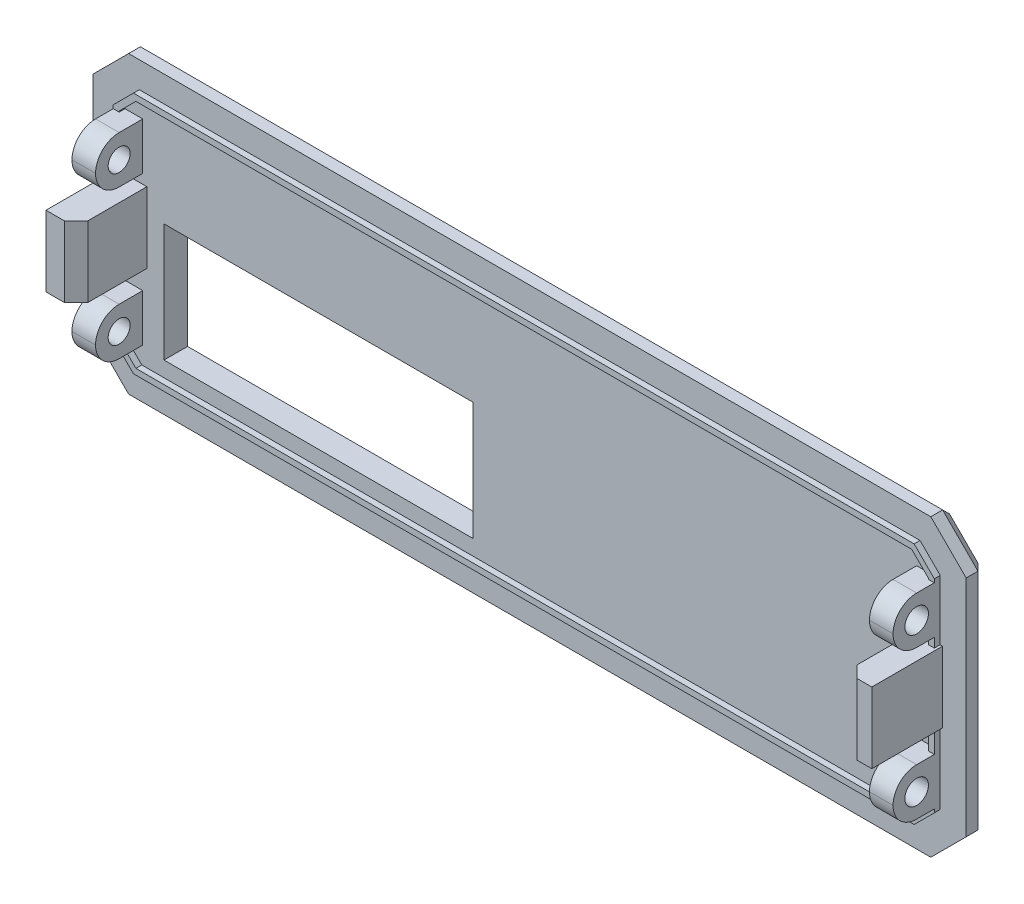
SolidWorks part; units mm, degrees
ref_plane "前视基准面" through (0, 0, 0) normal (0, 0, 1) x (1, 0, 0)
ref_plane "上视基准面" through (0, 0, 0) normal (0, 1, 0) x (1, 0, 0)
ref_plane "右视基准面" through (0, 0, 0) normal (1, 0, 0) x (0, 0, -1)
other "Configuration Table"
sketch "草图1" plane through (0, 0, 0) normal (0, 0, 1) x (1, 0, 0)
  line L0 (-39.7638, 4.7992) -> (-36.7638, 7.7992)
  line L5 (-36.7638, 7.7992) -> (31.2362, 7.7992)
  line L6 (-39.7638, 4.7992) -> (-39.7638, -14.2008)
  line L7 (-36.7638, -17.2008) -> (31.2362, -17.2008)
  line L8 (34.2362, 4.7992) -> (34.2362, -14.2008)
  line L9 (-39.7638, -14.2008) -> (-36.7638, -17.2008)
  line L10 (31.2362, -17.2008) -> (34.2362, -14.2008)
  line L11 (31.2362, 7.7992) -> (34.2362, 4.7992)
  point P0 (-39.7638, 7.7992)
  point P1 (34.2362, -17.2008)
  point P2 (-39.7638, -17.2008)
  point P3 (34.2362, 7.7992)
  dimension "D1" = 74
  dimension "D2" = 25
extrude "凸台-拉伸1" add sketch "草图1" along normal blind 2
chamfer "倒角1" distance 1 angle 45 8 edges at (-38.2638, 6.2992, 0) (-2.7638, -17.2008, 0) (-39.7638, -4.7008, 0) (-38.2638, -15.7008, 0) (32.7362, -15.7008, 0) (34.2362, -4.7008, 0) (32.7362, 6.2992, 0) (-2.7638, 7.7992, 0)
sketch "草图3" plane through (0, 0, 2) normal (0, 0, 1) x (1, 0, 0)
  line L0 (-36.7638, 7.7992) -> (31.2362, 7.7992) construction
  line L1 (-37.5638, 3.5992) -> (-35.5638, 3.5992)
  line L2 (-37.5638, 3.5992) -> (-37.5638, -0.4008)
  line L3 (-37.5638, -0.4008) -> (-35.5638, -0.4008)
  line L4 (-35.5638, 3.5992) -> (-35.5638, -0.4008)
  line L5 (-37.5638, -13.0008) -> (-35.5638, -13.0008)
  line L6 (-37.5638, -13.0008) -> (-37.5638, -9.0008)
  line L7 (-37.5638, -9.0008) -> (-35.5638, -9.0008)
  line L8 (-35.5638, -13.0008) -> (-35.5638, -9.0008)
  line L9 (32.0362, 3.5992) -> (30.0362, 3.5992)
  line L10 (32.0362, 3.5992) -> (32.0362, -0.4008)
  line L11 (32.0362, -0.4008) -> (30.0362, -0.4008)
  line L12 (30.0362, 3.5992) -> (30.0362, -0.4008)
  line L13 (32.0362, -13.0008) -> (30.0362, -13.0008)
  line L14 (32.0362, -13.0008) -> (32.0362, -9.0008)
  line L15 (32.0362, -9.0008) -> (30.0362, -9.0008)
  line L16 (30.0362, -13.0008) -> (30.0362, -9.0008)
  line L17 (-39.7638, -14.2008) -> (-39.7638, 4.7992) construction
  line L18 (34.2362, 4.7992) -> (34.2362, -14.2008) construction
  line L19 (31.2362, -17.2008) -> (-36.7638, -17.2008) construction
  dimension "D1" = 2
  dimension "D2" = 4
  dimension "D3" = 4.2
  dimension "D4" = 2.2
  dimension "D5" = 2.2
  dimension "D6" = 4.2
extrude "凸台-拉伸2" add sketch "草图3" along normal blind 4
fillet "圆角1" radius 2 8 edges at (31.0362, 3.5992, 6) (31.0362, -0.4008, 6) (31.0362, -9.0008, 6) (31.0362, -13.0008, 6) (-36.5638, -13.0008, 6) (-36.5638, -9.0008, 6) (-36.5638, 3.5992, 6) (-36.5638, -0.4008, 6)
sketch "草图4" plane through (32.0362, 0, 0) normal (1, 0, 0) x (0, 0, -1)
  circle A0 centre (-4, 1.5992) radius 1
  circle A1 centre (-4, -11.0008) radius 1
  dimension "D1" = 2
extrude "切除-拉伸1" cut sketch "草图4" against normal up to next (2 mm away) draft 2
sketch "草图5" plane through (-37.5638, 0, 0) normal (-1, 0, 0) x (0, 0, 1)
  circle A0 centre (4, 1.5992) radius 1
  circle A1 centre (4, -11.0008) radius 1
  dimension "D1" = 2
extrude "切除-拉伸2" cut sketch "草图5" against normal up to next (2 mm away) draft 2
sketch "草图8" plane through (0, 0, 2) normal (0, 0, 1) x (1, 0, 0)
  line L0 (-37.7638, 3.9708) -> (-37.7638, -13.3724) construction
  line L1 (-37.7638, -1.2008) -> (-35.2138, -1.2008)
  line L2 (-37.7638, -1.2008) -> (-37.7638, -7.2008)
  line L3 (-37.7638, -7.2008) -> (-35.2138, -7.2008)
  line L4 (-35.2138, -1.2008) -> (-35.2138, -7.2008)
  line L6 (32.2362, -13.3724) -> (32.2362, 3.9708) construction
  line L7 (32.2362, -1.2008) -> (29.9862, -1.2008)
  line L8 (32.2362, -1.2008) -> (32.2362, -7.2008)
  line L9 (32.2362, -7.2008) -> (29.9862, -7.2008)
  line L10 (29.9862, -1.2008) -> (29.9862, -7.2008)
  line L12 (-36.7638, -17.2008) -> (31.2362, -17.2008) construction
  dimension "D1" = 10
  dimension "D2" = 6
  dimension "D3" = 2.55
  dimension "D4" = 2.25
extrude "凸台-拉伸5" add sketch "草图8" along normal blind 6
chamfer "倒角3" distance 1 angle 45 2 edges at (29.9862, -4.2008, 8) (-35.2138, -4.2008, 8)
sketch "草图10" plane through (0, 0, 0) normal (0, 0, -1) x (-1, 0, 0)
  line L0 (36.7638, -17.2008) -> (-31.2362, -17.2008) construction
  line L1 (7.5638, -3.2008) -> (33.7638, -3.2008)
  line L2 (7.5638, -3.2008) -> (7.5638, -13.2008)
  line L3 (7.5638, -13.2008) -> (33.7638, -13.2008)
  line L4 (33.7638, -3.2008) -> (33.7638, -13.2008)
  line L5 (39.7638, 4.7992) -> (39.7638, -14.2008) construction
  dimension "D1" = 4
  dimension "D2" = 10
  dimension "D3" = 6
  dimension "D4" = 26.2
extrude "切除-拉伸3" cut sketch "草图10" against normal up to next
sketch "草图11" plane through (0, 0, 2) normal (0, 0, 1) x (1, 0, 0)
  line L8 (30.1178, 5.0992) -> (-35.6455, 5.0992)
  line L9 (-35.6455, 5.0992) -> (-37.0638, 3.6808)
  line L10 (-37.0638, 3.6808) -> (-37.0638, -13.0824)
  line L11 (-37.0638, -13.0824) -> (-35.6455, -14.5008)
  line L12 (-35.6455, -14.5008) -> (30.1178, -14.5008)
  line L13 (30.1178, -14.5008) -> (31.5362, -13.0824)
  line L14 (31.5362, -13.0824) -> (31.5362, 3.6808)
  line L15 (31.5362, 3.6808) -> (30.1178, 5.0992)
  line L16 (30.3249, 5.5992) -> (-35.8526, 5.5992)
  line L17 (-35.8526, 5.5992) -> (-37.5638, 3.8879)
  line L18 (-37.5638, 3.8879) -> (-37.5638, -13.2895)
  line L19 (-37.5638, -13.2895) -> (-35.8526, -15.0008)
  line L20 (-35.8526, -15.0008) -> (30.3249, -15.0008)
  line L21 (30.3249, -15.0008) -> (32.0362, -13.2895)
  line L22 (32.0362, -13.2895) -> (32.0362, 3.8879)
  line L23 (32.0362, 3.8879) -> (30.3249, 5.5992)
  line L24 (30.3249, 5.5992) -> (-35.8526, 5.5992)
  line L25 (-35.8526, 5.5992) -> (-37.5638, 3.8879)
  line L26 (-37.5638, 3.8879) -> (-37.5638, -13.2895)
  line L27 (-37.5638, -13.2895) -> (-35.8526, -15.0008)
  line L28 (-35.8526, -15.0008) -> (30.3249, -15.0008)
  line L29 (30.3249, -15.0008) -> (32.0362, -13.2895)
  line L30 (32.0362, -13.2895) -> (32.0362, 3.8879)
  line L31 (32.0362, 3.8879) -> (30.3249, 5.5992)
  dimension "D1" = 2.2
  dimension "D2" = 0.5
extrude "凸台-拉伸7" add sketch "草图11" along normal blind 0.5
